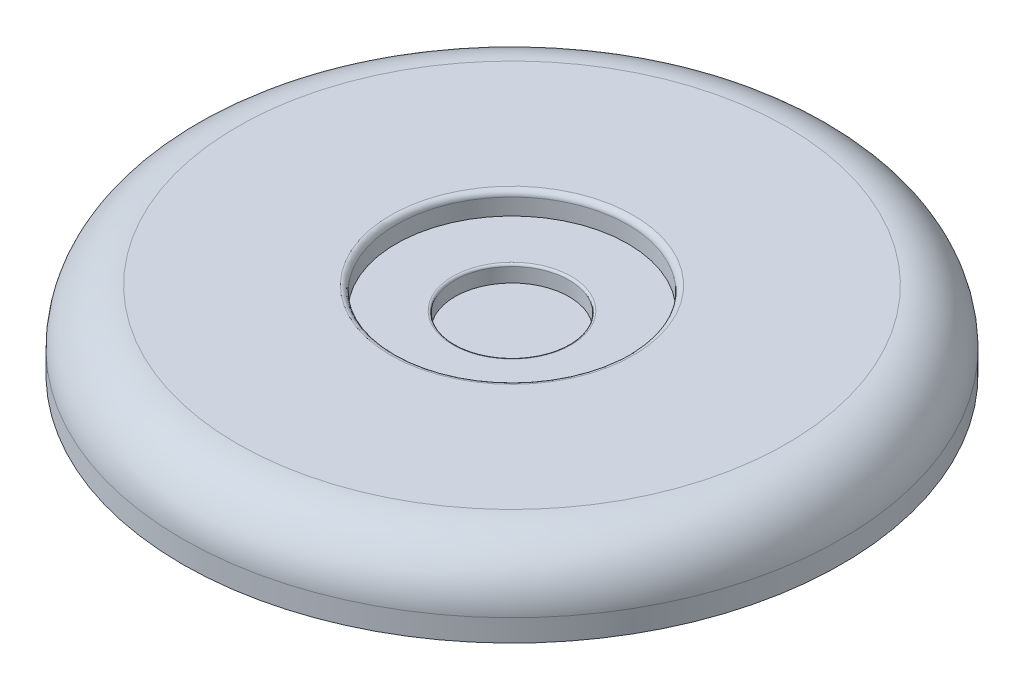
SolidWorks part; units mm, degrees
ref_plane "Front Plane" through (0, 0, 0) normal (0, 0, 1) x (1, 0, 0)
ref_plane "Top Plane" through (0, 0, 0) normal (0, 1, 0) x (1, 0, 0)
ref_plane "Right Plane" through (0, 0, 0) normal (1, 0, 0) x (0, 0, -1)
sketch "Sketch1" plane through (0, 0, 0) normal (1, 0, 0) x (0, 0, -1)
  line L2 (0, 0) -> (-30, 0)
  line L3 (-10.55, 7) -> (-10.55, 5)
  line L4 (-10.55, 5) -> (0, 5)
  line L5 (0, 5) -> (0, 0)
  line L6 (-10.55, 7) -> (-20.1025, 7)
  line L7 (-30, 0) -> (-30, 7)
  line L8 (-30, 7) -> (-20.1025, 7)
  dimension "D3" = 10.55
  dimension "D1" = 2
  dimension "D2" = 5
  dimension "D4" = 30
revolve "Revolve1" add sketch "Sketch1" angle 360 about L5
fillet "Fillet1" radius 0.5 1 edges at (0, 7, 10.55)
sketch "Sketch2" plane through (0, 5, 0) normal (0, 1, 0) x (1, 0, 0)
  circle A0 centre (0, 0) radius 5.2
  dimension "D1" = 10.4
extrude "Cut-Extrude1" cut sketch "Sketch2" against normal blind 1.5
fillet "Fillet2" radius 0.2 1 edges at (0, 5, 5.2)
fillet "Fillet3" radius 5 1 edges at (0, 7, 30)
